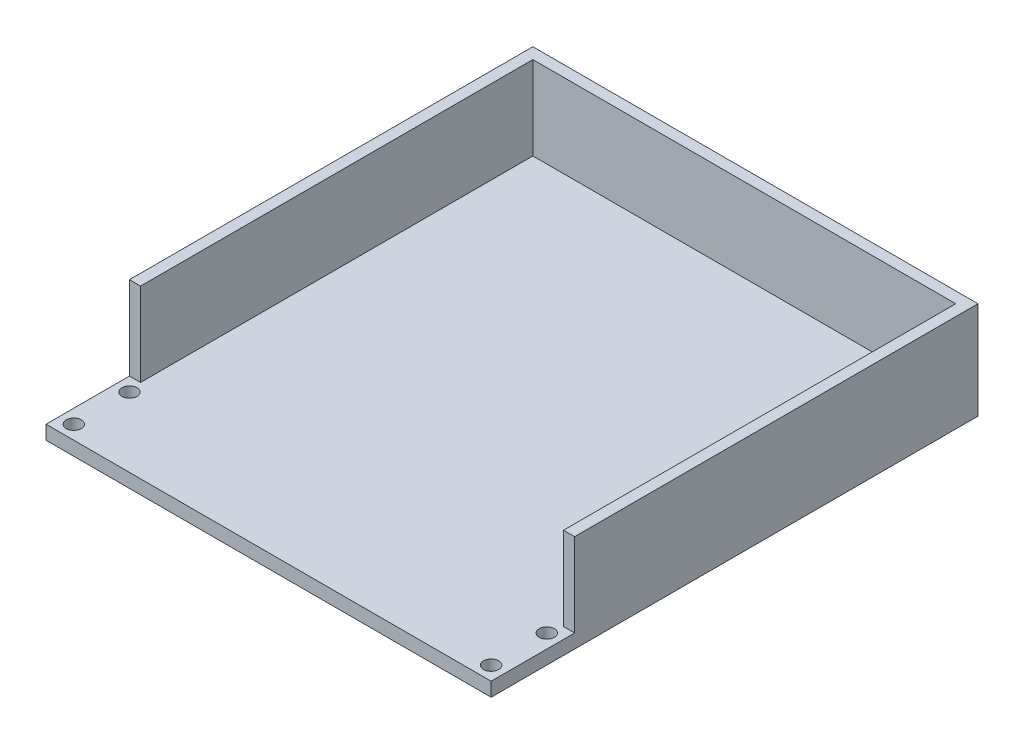
SolidWorks part; units mm, degrees
material "ABS"
ref_plane "Front Plane" through (0, 0, 0) normal (0, 0, 1) x (1, 0, 0)
ref_plane "Top Plane" through (0, 0, 0) normal (0, 1, 0) x (1, 0, 0)
ref_plane "Right Plane" through (0, 0, 0) normal (1, 0, 0) x (0, 0, -1)
other "Center of Mass"
sketch "Sketch1" plane through (0, 0, 0) normal (0, 1, 0) x (1, 0, 0)
  line L0 (-44.45, -60.325) -> (44.45, -60.325)
  line L1 (-50.8, -50.8) -> (50.8, -50.8)
  line L2 (-50.8, -50.8) -> (-50.8, 50.8)
  line L3 (-50.8, 50.8) -> (50.8, 50.8)
  line L4 (50.8, -50.8) -> (50.8, 50.8)
  line L5 (-50.8, -50.8) -> (50.8, 50.8) construction
  line L6 (-50.8, 50.8) -> (50.8, -50.8) construction
  line L7 (-50.8, -50.8) -> (-44.45, -50.8)
  line L8 (-50.8, -50.8) -> (-50.8, -60.325)
  line L9 (-50.8, -60.325) -> (-44.45, -60.325)
  line L10 (-44.45, -50.8) -> (-44.45, -60.325)
  line L11 (50.8, -50.8) -> (44.45, -50.8)
  line L12 (50.8, -50.8) -> (50.8, -60.325)
  line L13 (50.8, -60.325) -> (44.45, -60.325)
  line L14 (44.45, -50.8) -> (44.45, -60.325)
  point P0 (0, 0)
  dimension "D1" = 101.6
  dimension "D2" = 101.6
  dimension "D3" = 9.525
  dimension "D4" = 6.35
extrude "Boss-Extrude1" add sketch "Sketch1" along normal blind 3.175 contours L1 L4 L3 L2 | L10 L1 L8 L9 | L1 L14 L13 L12 region at (-47.625, 0, 55.5625) region at (47.625, 0, 55.5625) region at (0, 0, 0)
hole_wizard "#8-32 Tapped Hole1" positions "Sketch6" profile "Sketch7" tap size "#8-32" standard "ANSI Inch" end condition through all
sketch "Sketch6" plane through (0, 0, 0) normal (0, -1, 0) x (-1, 0, 0)
  line L0 (-47.625, -44.45) -> (-47.625, -57.15) construction
  line L2 (47.625, -44.45) -> (47.625, -57.15) construction
  line L3 (44.45, -50.8) -> (47.625, -50.8) construction
  line L4 (47.625, -50.8) -> (50.8, -50.8) construction
  line L5 (50.8, -60.325) -> (50.8, 50.8) construction
  line L7 (44.45, -50.8) -> (-44.45, -50.8) construction
  line L8 (-44.45, -50.8) -> (-47.625, -50.8) construction
  line L9 (-47.625, -50.8) -> (-50.8, -50.8) construction
  line L10 (-50.8, -60.325) -> (-50.8, 50.8) construction
  point P0 (-47.625, -57.15)
  point P2 (-47.625, -44.45)
  point P4 (47.625, -57.15)
  point P6 (47.625, -44.45)
  dimension "D1" = 12.7
sketch "Sketch7" plane through (47.625, 0, 57.15) normal (1, 0, 0) x (0, 0, -1)
  line L0 (0, 0) -> (0, 3.175)
  line L1 (0, 3.175) -> (1.7272, 3.175)
  line L2 (1.7272, 3.175) -> (1.7272, 0)
  line L5 (1.7272, 0) -> (0, 0)
  line L11 (0, -6.35) -> (0, 107.95) construction
  dimension "Thru Tap Drill Dia." = 3.4544
  dimension "Thru Tap Drill Depth" = 3.175
cosmetic thread "Hole Thread1" parameters "D2"=4.1656
cosmetic thread "Hole Thread2" parameters "D2"=4.1656
cosmetic thread "Hole Thread3" parameters "D2"=4.1656
cosmetic thread "Hole Thread4" parameters "D2"=4.1656
sketch "Sketch8" plane through (0, 3.175, 0) normal (0, 1, 0) x (1, 0, 0)
  line L6 (-50.8, 50.8) -> (50.8, 50.8)
  line L7 (50.8, 50.8) -> (50.8, -41.275)
  line L8 (50.8, -60.325) -> (50.8, 50.8) construction
  line L9 (48.26, 48.26) -> (48.26, -60.325)
  line L10 (-48.26, 48.26) -> (48.26, 48.26)
  line L11 (-48.26, -60.325) -> (-48.26, 48.26)
  line L12 (48.26, 48.26) -> (48.26, -41.275)
  line L13 (-48.26, 48.26) -> (48.26, 48.26)
  line L14 (-48.26, -41.275) -> (-48.26, 48.26)
  line L15 (50.8, -41.275) -> (48.26, -41.275)
  line L16 (-48.26, -41.275) -> (-50.8, -41.275)
  line L17 (-50.8, -60.325) -> (-50.8, 50.8) construction
  line L18 (-50.8, 50.8) -> (-50.8, -41.275)
  line L19 (-44.45, -50.8) -> (-44.45, -41.275) construction
  line L20 (-44.45, -41.275) -> (-48.26, -41.275) construction
  line L21 (-44.45, -50.8) -> (-44.45, -60.325) construction
  line L22 (-48.26, -60.325) -> (-48.26, -41.275) construction
  line L23 (48.26, -41.275) -> (48.26, -60.325) construction
  dimension "D1" = 2.54
extrude "Boss-Extrude2" add sketch "Sketch8" along normal blind 19.05
extrude "Boss-Extrude3" add sketch "Sketch1<3>" along normal up to surface (3.175 mm away) contours L14 L1 L10 L0 region at (0, 0, 55.5625) up to face at (0, 3.175, 34.29)
sketch "Sketch1<3>" plane through (0, 0, 0) normal (0, 1, 0) x (1, 0, 0) same geometry as "Sketch1"
